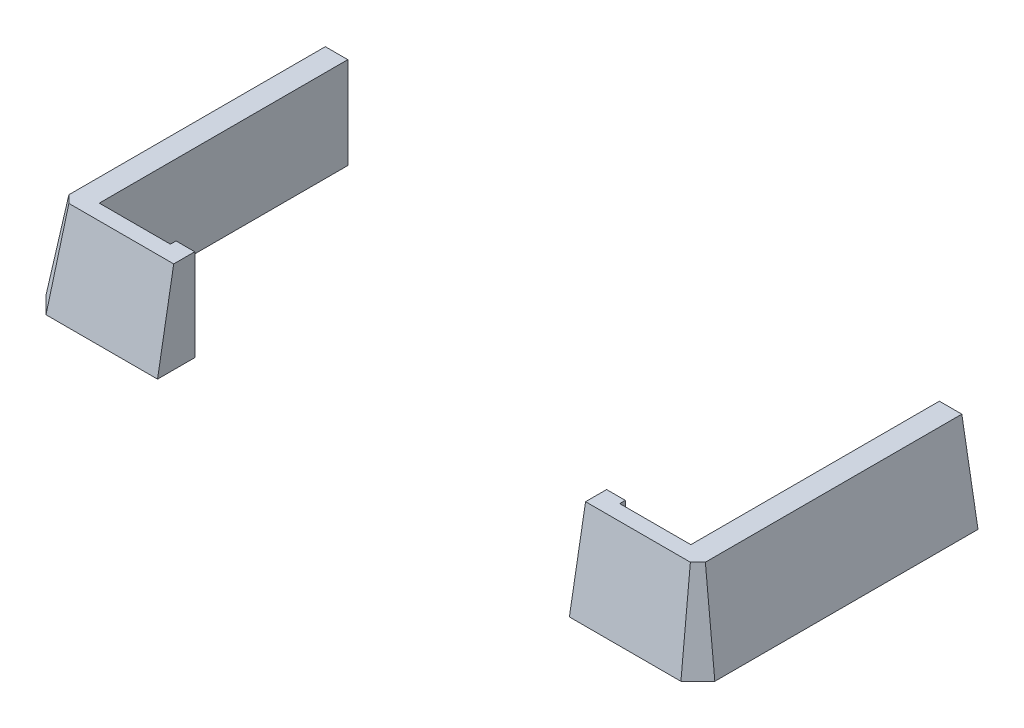
SolidWorks part; units mm, degrees
ref_plane "Front Plane" through (0, 0, 0) normal (0, 0, 1) x (1, 0, 0)
ref_plane "Top Plane" through (0, 0, 0) normal (0, 1, 0) x (1, 0, 0)
ref_plane "Right Plane" through (0, 0, 0) normal (1, 0, 0) x (0, 0, -1)
sketch "Sketch1" plane through (0, 0, 0) normal (0, 1, 0) x (1, 0, 0)
  line L9 (0, 0) -> (-158, 0) construction
  line L10 (0, 0) -> (0, 76.9384) construction
  line L11 (0, 0) -> (-158, 0) construction
  line L12 (-158, 99.7575) -> (-158, -30.0025) construction
  line L14 (-158, 99.7575) -> (-170, 99.7575) construction
  line L16 (-170, 99.7575) -> (-170, -41.2425) construction
  line L17 (-170, -41.2425) -> (-158, -41.2425) construction
  line L19 (-158, -30.0025) -> (-105, -30.0025) construction
  line L20 (-105, -30.0025) -> (-105, -41.2425) construction
  line L21 (-105, -41.2425) -> (-158, -41.2425) construction
  line L22 (-158, -30.0025) -> (-158, -41.2425) construction
  dimension "D5" = 158
  dimension "D6" = 12
  dimension "D7" = 53
  dimension "D8" = 11.24
  dimension "D9" = 41.2425
  dimension "D10" = 141
ref_plane "Plane1" through (0, -25, 0) normal (0, 1, 0) x (1, 0, 0)
ref_plane "Plane2" through (0, 24, 0) normal (0, 1, 0) x (1, 0, 0)
sketch "Sketch3" plane through (0, 24, 0) normal (0, 1, 0) x (1, 0, 0)
  line L0 (-170, 99.7575) -> (-158, 99.7575)
  line L1 (-158, 99.7575) -> (-158, -30.0025)
  line L4 (-110, -41.2425) -> (-166, -41.2425)
  line L5 (-170, -37.2425) -> (-170, 99.7575)
  line L6 (-166, -41.2425) -> (-170, -37.2425)
  line L8 (-120, -30) -> (-120, -33.0025)
  line L9 (-120, -33.0025) -> (-158, -33.0025)
  line L10 (-158, -33.0025) -> (-158, -30.0025)
  line L13 (-120, -30) -> (-110, -30)
  line L14 (-110, -30) -> (-110, -41.2425)
  point P11 (-170, -41.2425)
  dimension "D1" = 3
extrude "Boss-Extrude1" add sketch "Sketch3" against normal up to surface (49 mm away) up to plane "Plane1"
draft "Draft1" type of draft neutral plane draft angle 10 faces to draft 3 face at (-138, -0.5, 41.2425) face at (-168, -0.5, 39.2425) face at (-170, -0.5, -31.2575) neutral plane through (0, 24, 0) neutral plane normal (0, 1, 0) parameters "D1"=10
mirror "Mirror2" about plane through (0, 0, 0) normal (1, 0, 0) of bodies 105
